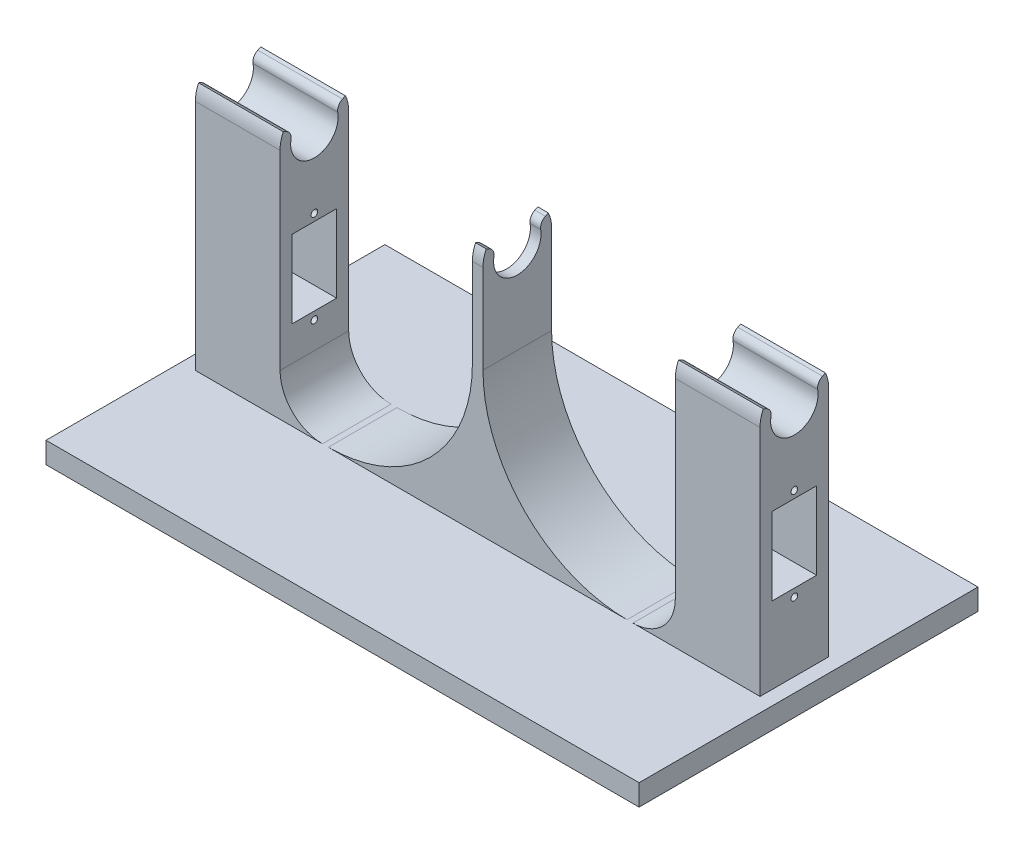
SolidWorks part; units mm, degrees
ref_plane "Front Plane" through (0, 0, 0) normal (0, 0, 1) x (1, 0, 0)
ref_plane "Top Plane" through (0, 0, 0) normal (0, 1, 0) x (1, 0, 0)
ref_plane "Right Plane" through (0, 0, 0) normal (1, 0, 0) x (0, 0, -1)
sketch "Sketch1" plane through (0, 0, 0) normal (0, 1, 0) x (1, 0, 0)
  line L1 (-88.9, -50.8) -> (88.9, -50.8)
  line L2 (-88.9, -50.8) -> (-88.9, 50.8)
  line L3 (-88.9, 50.8) -> (88.9, 50.8)
  line L4 (88.9, -50.8) -> (88.9, 50.8)
  line L5 (-88.9, -50.8) -> (88.9, 50.8) construction
  line L6 (-88.9, 50.8) -> (88.9, -50.8) construction
  point P0 (0, 0)
  dimension "D1" = 177.8
  dimension "D2" = 101.6
extrude "Boss-Extrude1" add sketch "Sketch1" along normal blind 6.35
sketch "Sketch2" plane through (-88.9, 0, 0) normal (-1, 0, 0) x (0, 0, 1)
  line L0 (-50.8, 0) -> (50.8, 0) construction
  line L1 (-10.287, 0) -> (10.287, 0)
  line L2 (-10.287, 0) -> (-10.287, 76.2)
  line L4 (10.287, 0) -> (10.287, 76.2)
  line L5 (0, 76.2) -> (0, 0) construction
  line L6 (0, 76.2) -> (9.3232, 80.5475)
  line L7 (0, 76.2) -> (-9.3232, 80.5475)
  arc A1 (10.287, 76.2) -> (9.3232, 80.5475) centre (0, 76.2) ccw
  arc A2 (-6.4457, 79.2057) -> (6.4457, 79.2057) centre (0, 76.2) ccw
  arc A3 (-9.3232, 80.5475) -> (-10.287, 76.2) centre (0, 76.2) ccw
  line M8 (50.8, 6.35) -> (-50.8, 6.35)
  dimension "D2" = 3.175
  dimension "D3" = 14.224
  dimension "D1" = 76.2
  dimension "D4" = 130
extrude "Boss-Extrude2" add sketch "Sketch2" against normal up to surface (177.8 mm away) contours A2 L5 L4 A1 L6 M8 | L5 A2 L7 A3 L2 M8 region at (-88.9, 40.0825, -5.3246) region at (-88.9, 40.0825, 5.3246) up to face at (88.9, 3.175, 0)
sketch "Sketch3" plane through (0, 6.35, 0) normal (0, 1, 0) x (1, 0, 0)
  line L0 (-1.5875, 50.8) -> (-1.5875, -50.8)
  line L1 (88.9, 50.8) -> (-88.9, 50.8) construction
  line L2 (-88.9, -50.8) -> (88.9, -50.8) construction
  line L3 (1.5875, 50.8) -> (1.5875, -50.8)
  line L4 (59.2455, 50.8) -> (59.2455, -50.8)
  line L5 (84.6455, 50.8) -> (84.6455, -50.8)
  line L6 (-1.5875, 50.8) -> (1.5875, 50.8) construction
  line L7 (0, 50.8) -> (0, 0) construction
  line L8 (1.5875, -50.8) -> (59.2455, -50.8)
  line L9 (1.5875, 50.8) -> (59.2455, 50.8)
  line L10 (84.6455, 50.8) -> (88.9, 50.8)
  line L11 (88.9, 50.8) -> (88.9, -50.8)
  line L12 (88.9, -50.8) -> (84.6455, -50.8)
  line L13 (-84.6455, -50.8) -> (-84.6455, 50.8)
  line L14 (-84.6455, 50.8) -> (-88.9, 50.8)
  line L15 (-88.9, 50.8) -> (-88.9, -50.8)
  line L16 (-88.9, -50.8) -> (-84.6455, -50.8)
  line L17 (-59.2455, 50.8) -> (-59.2455, -50.8)
  line L18 (-59.2455, -50.8) -> (-1.5875, -50.8)
  line L19 (-1.5875, 50.8) -> (-59.2455, 50.8)
  dimension "D1" = 3.175
  dimension "D2" = 25.4
  dimension "D3" = 25.4
  dimension "D4" = 57.658
  dimension "D5" = 57.658
extrude "Cut-Extrude1" cut sketch "Sketch3" along normal through all from surface starting at face at (0, 6.35, -30.5435)
fillet "Fillet1" radius 43.18 2 edges at (1.5875, 6.35, 0) (-1.5875, 6.35, 0)
fillet "Fillet2" radius 12.7 2 edges at (59.2455, 6.35, 0) (-59.2455, 6.35, 0)
fillet "Fillet3" [suppressed] radius 2.286
sketch "Sketch5" plane through (59.2455, 0, 0) normal (-1, 0, 0) x (0, 0, 1)
  line L0 (0, 76.2) -> (0, 52.582) construction
  line L1 (-6.6675, 52.582) -> (6.6675, 52.582)
  line L2 (-6.6675, 52.582) -> (-6.6675, 29.341)
  line L3 (-6.6675, 29.341) -> (6.6675, 29.341)
  line L4 (6.6675, 52.582) -> (6.6675, 29.341)
  circle A0 centre (0, 54.7) radius 1
  circle A1 centre (0, 27.014) radius 1
  point P7 (0, 46.482)
  dimension "D7" = 2
  dimension "D8" = 2
  dimension "D1" = 13.335
  dimension "D2" = 23.241
  dimension "D3" = 6.1
  dimension "D4" = 29.718
  dimension "D5" = 21.5
  dimension "D6" = 27.686
extrude "Cut-Extrude2" cut sketch "Sketch5" against normal through all
extrude "Cut-Extrude3" cut sketch "Sketch5<2>" along normal through all from surface starting at face at (-59.2455, 62.4993, 0)
sketch "Sketch5<2>" plane through (59.2455, 0, 0) normal (-1, 0, 0) x (0, 0, 1) same geometry as "Sketch5"
fillet "Fillet4" radius 2.54 6 edges at (-71.9455, 79.2057, 6.4457) (-71.9455, 79.2057, -6.4457) (0, 79.2057, -6.4457) (0, 79.2057, 6.4457) (71.9455, 79.2057, 6.4457) (71.9455, 79.2057, -6.4457)
